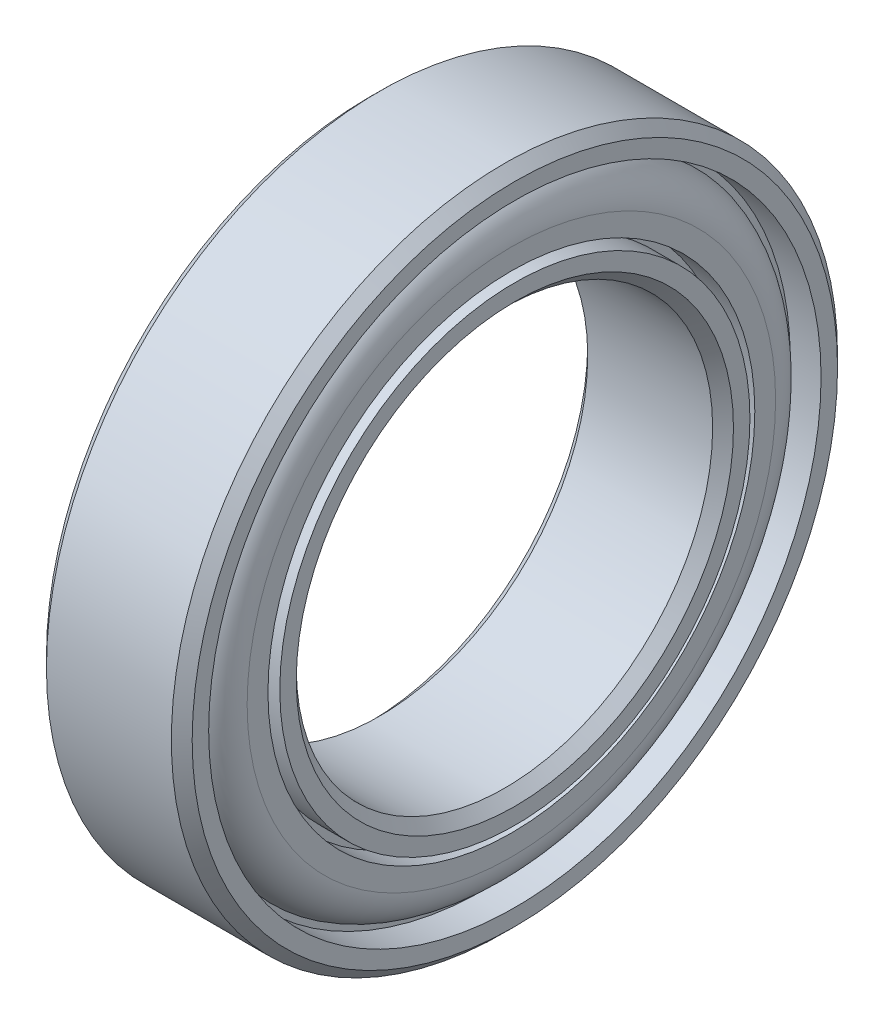
SolidWorks part; units mm, degrees
ref_plane "Front Plane" through (0, 0, 0) normal (0, 0, 1) x (1, 0, 0)
ref_plane "Top Plane" through (0, 0, 0) normal (0, 1, 0) x (1, 0, 0)
ref_plane "Right Plane" through (0, 0, 0) normal (1, 0, 0) x (0, 0, -1)
sketch "Sketch2" plane through (0, 0, 0) normal (0, 0, 1) x (1, 0, 0)
  line L0 (0, 0) -> (-23.8789, 0) construction
  line L1 (0, 13) -> (0, 0) construction
  line L2 (-3.5, 16) -> (3.5, 16)
  line L3 (-3.5, 16) -> (-3.5, 10)
  line L4 (-3.5, 10) -> (3.5, 10)
  line L5 (3.5, 16) -> (3.5, 10)
  line L6 (-3.5, 16) -> (3.5, 10) construction
  line L7 (-3.5, 10) -> (3.5, 16) construction
  point P3 (0, 13)
  dimension "D1" = 20
  dimension "D2" = 32
  dimension "D3" = 7
revolve "Revolve1" add sketch "Sketch2" angle 360 about L0
sketch "Sketch4" plane through (0, 0, 0) normal (0, 0, 1) x (1, 0, 0)
  line L0 (6.5942, 14.7079) -> (2.0229, 14.7079)
  line L1 (2.0229, 14.7079) -> (2.0229, 14.424)
  line L2 (2.0229, 14.424) -> (3.3324, 14.424)
  line L3 (3.3324, 14.424) -> (3.3324, 11.6927)
  line L4 (3.3324, 11.6927) -> (2.0229, 11.6927)
  line L5 (2.0229, 11.6927) -> (2.0229, 11.2913)
  line L6 (2.0229, 11.2913) -> (6.5942, 11.2913)
  line L7 (6.5942, 11.2913) -> (6.5942, 14.7079)
  line L8 (2.0229, 14.424) -> (2.0229, 11.6927) construction
  line L9 (0, 16) -> (0, 0) construction
  line L10 (3.5, 16) -> (-3.5, 16) construction
  line L11 (-2.0229, 14.424) -> (-2.0229, 11.6927) construction
  line L12 (-6.5942, 11.2913) -> (-6.5942, 14.7079)
  line L13 (-2.0229, 11.2913) -> (-6.5942, 11.2913)
  line L14 (-2.0229, 11.6927) -> (-2.0229, 11.2913)
  line L15 (-3.3324, 11.6927) -> (-2.0229, 11.6927)
  line L16 (-3.3324, 14.424) -> (-3.3324, 11.6927)
  line L17 (-2.0229, 14.424) -> (-3.3324, 14.424)
  line L18 (-2.0229, 14.7079) -> (-2.0229, 14.424)
  line L19 (-6.5942, 14.7079) -> (-2.0229, 14.7079)
  line L20 (0, 0) -> (9.4504, 0) construction
revolve "Cut-Revolve1" cut sketch "Sketch4" angle 360 about L20
fillet "Fillet1" radius 1.8 2 edges at (-3.3324, 0, 14.424) (3.3324, 0, 14.424)
chamfer "Chamfer1" distance 0.5 angle 45 4 edges at (-3.5, 0, -10) (-3.5, 0, -16) (3.5, 0, -16) (3.5, 0, -10)
